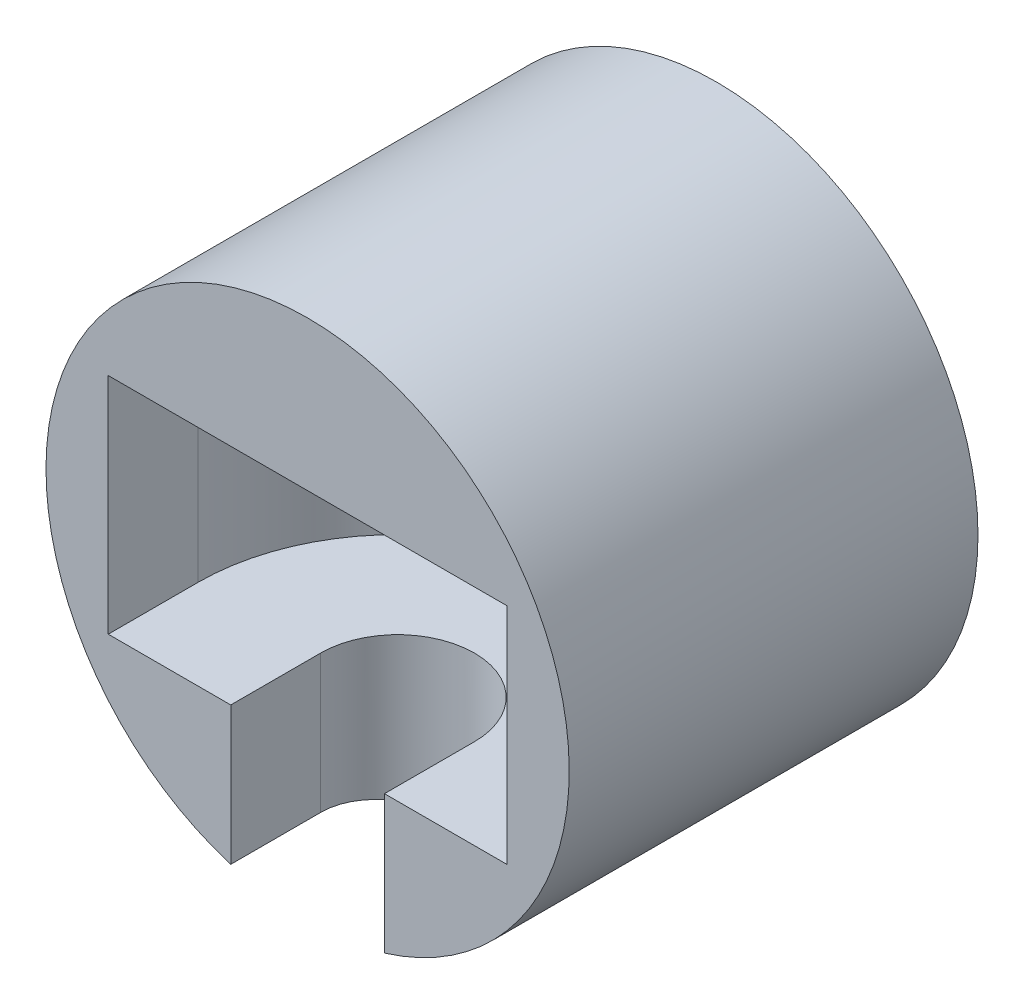
SolidWorks part; units mm, degrees
ref_plane "Front Plane" through (0, 0, 0) normal (0, 0, 1) x (1, 0, 0)
ref_plane "Top Plane" through (0, 0, 0) normal (0, 1, 0) x (1, 0, 0)
ref_plane "Right Plane" through (0, 0, 0) normal (1, 0, 0) x (0, 0, -1)
sketch "Sketch1" plane through (0, 0, 0) normal (0, 0, 1) x (1, 0, 0)
  circle A0 centre (0, 0) radius 3
  circle A1 centre (0, 0) radius 16
extrude "Boss-Extrude1" add sketch "Sketch1" along normal blind 25
sketch "Sketch2" plane through (0, 0, 0) normal (0, 1, 0) x (1, 0, 0)
  line L10 (12.193, -25) -> (-12.193, -25)
  line L19 (-12.193, -19.5) -> (-12.193, -25)
  line L20 (12.193, -19.5) -> (12.193, -25)
  line L21 (-6.9763, -9.5) -> (6.9763, -9.5)
  arc A8 (12.193, -19.5) -> (6.9763, -9.5) centre (0, -19.5) ccw
  arc A9 (-6.9763, -9.5) -> (-12.193, -19.5) centre (0, -19.5) ccw
extrude "Cut-Extrude1" cut sketch "Sketch2" against normal mid plane 13.7
sketch "Sketch3" plane through (0, 0, 0) normal (0, 1, 0) x (1, 0, 0)
  line L9 (-4.7, -19.5) -> (-4.7, -25)
  line L10 (-4.7, -25) -> (4.7, -25)
  line L11 (4.7, -19.5) -> (4.7, -25)
  arc A4 (4.7, -19.5) -> (-4.7, -19.5) centre (0, -19.5) ccw
extrude "Cut-Extrude2" cut sketch "Sketch3" against normal up to surface (15.2941 mm away) up to face at (16, 0, 25)
